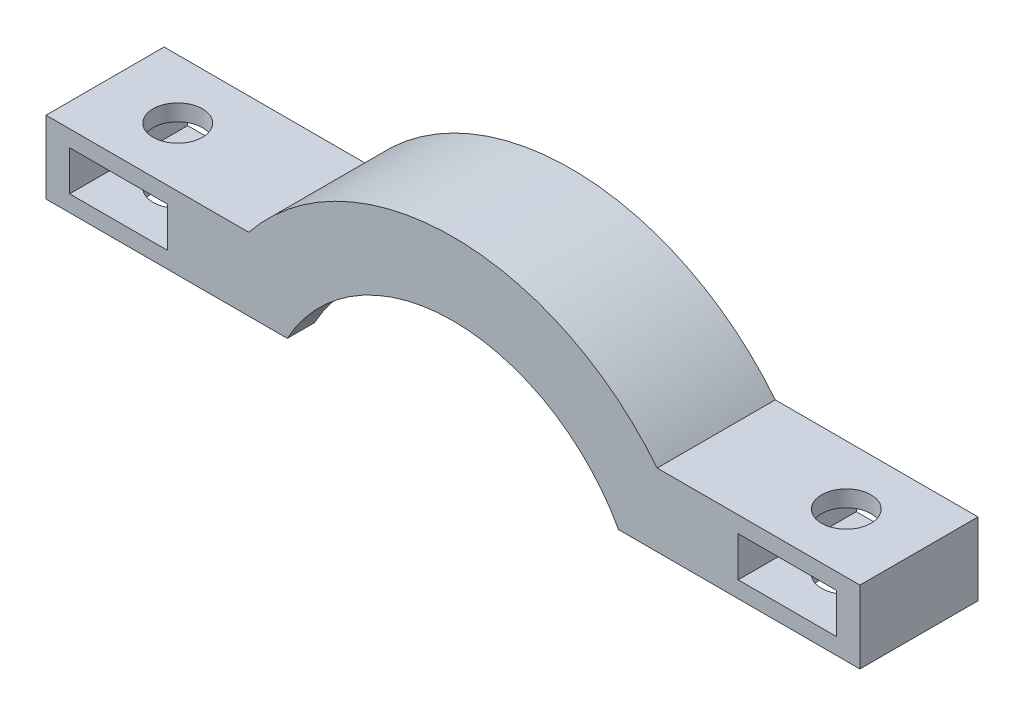
SolidWorks part; units mm, degrees
ref_plane "Front Plane" through (0, 0, 0) normal (0, 0, 1) x (1, 0, 0)
ref_plane "Top Plane" through (0, 0, 0) normal (0, 1, 0) x (1, 0, 0)
ref_plane "Right Plane" through (0, 0, 0) normal (1, 0, 0) x (0, 0, -1)
sketch "Sketch1" plane through (0, 0, 0) normal (0, 0, 1) x (1, 0, 0)
  circle A0 centre (0, 0) radius 18.288
  dimension "D1" = 36.576
extrude "Boss-Extrude1" add sketch "Sketch1" along normal blind 19.05
sketch "Sketch3" plane through (0, 0, 19.05) normal (0, 0, 1) x (1, 0, 0)
  circle A0 centre (0, 0) radius 13.208
  dimension "D2" = 26.416
extrude "Cut-Extrude1" cut sketch "Sketch3" against normal through all
ref_plane "Plane2" through (0, -13.716, 0) normal (0, 1, 0) x (1, 0, 0)
sketch "Sketch15" plane through (0, -13.716, 0) normal (0, 1, 0) x (1, 0, 0)
  line L0 (0, -19.05) -> (0, 0) construction
  line L1 (-9.525, -0.762) -> (9.525, -0.762)
  line L2 (-9.525, -0.762) -> (-9.525, -18.288)
  line L3 (-9.525, -18.288) -> (9.525, -18.288)
  line L4 (9.525, -0.762) -> (9.525, -18.288)
  line L5 (-9.525, -0.762) -> (9.525, -18.288) construction
  line L6 (-9.525, -18.288) -> (9.525, -0.762) construction
  line L7 (-13.208, -19.05) -> (13.208, -19.05) construction
  line L8 (18.288, 0) -> (-18.288, 0) construction
  point P0 (0, -9.525)
  dimension "D1" = 19.05
  dimension "D2" = 0.762
  dimension "D3" = 0.762
extrude "Boss-Extrude3" add sketch "Sketch15" against normal blind 15.24
sketch "Sketch16" plane through (0, 0, 18.288) normal (0, 0, 1) x (1, 0, 0)
  line L0 (-9.525, -28.956) -> (-9.525, -15.6117) construction
  line L1 (-5.715, -25.5076) -> (5.715, -25.5076)
  line L2 (-5.715, -25.5076) -> (-5.715, -19.6656)
  line L3 (-5.715, -19.6656) -> (5.715, -19.6656)
  line L4 (5.715, -25.5076) -> (5.715, -19.6656)
  line L5 (-5.715, -25.5076) -> (5.715, -19.6656) construction
  line L6 (-5.715, -19.6656) -> (5.715, -25.5076) construction
  point P0 (0, -22.5866)
  dimension "D1" = 5.842
  dimension "D2" = 11.43
  dimension "D3" = 3.81
extrude "Cut-Extrude4" cut sketch "Sketch16" against normal through all
chamfer "Chamfer1" distance 5.08 angle 58 1 edges at (0, -28.956, 0.762) first distance on face at (0, -28.956, 9.525)
hole_wizard "1/4 Clearance Hole1" positions "Sketch18" profile "Sketch17" hole size "1/4" standard "ANSI Inch" end condition up to next
sketch "Sketch18" plane through (0, -28.956, 0) normal (0, -1, 0) x (-1, 0, 0)
  line L0 (0, -18.288) -> (0, -0.762) construction
  point P0 (0, -12.0214)
sketch "Sketch17" plane through (0, -28.956, 12.0214) normal (1, 0, 0) x (0, 0, -1)
  line L0 (0, 0) -> (0, 3.4484)
  line L1 (0, 3.4484) -> (3.3782, 3.4484)
  line L2 (3.3782, 3.4484) -> (3.3782, 0)
  line L5 (3.3782, 0) -> (0, 0)
  line L11 (0, -6.35) -> (0, 107.95) construction
  dimension "Thru Hole Dia." = 6.7564
  dimension "Thru Hole Depth" = 3.4484
sketch "Sketch19" plane through (0, 0, 19.05) normal (0, 0, 1) x (1, 0, 0)
  circle A0 centre (0, 0) radius 18.288
  circle A1 centre (0, 0) radius 13.208
extrude "Cut-Extrude5" cut sketch "Sketch19" against normal up to surface (0.762 mm away) up to face at (0, -22.5866, 18.288)
sketch "Sketch20" plane through (0, 0, 18.288) normal (0, 0, 1) x (1, 0, 0)
  circle A0 centre (0, 0) radius 18.288
extrude "Cut-Extrude6" cut sketch "Sketch20" against normal blind 2.54
sketch "Sketch21" plane through (0, 0, 0) normal (0, 0, -1) x (-1, 0, 0)
  circle A0 centre (0, 0) radius 18.288
extrude "Cut-Extrude7" cut sketch "Sketch21" against normal offset from surface (7.493 mm away) 8.255 up to face at (0, 0, 15.748)
sketch "Sketch22" plane through (0, -13.716, 0) normal (0, 1, 0) x (1, 0, 0)
  line L0 (9.525, -7.493) -> (9.525, -0.762) construction
  line L1 (-9.525, -0.762) -> (9.525, -0.762)
  line L2 (-9.525, -0.762) -> (-9.525, -4.953)
  line L3 (-9.525, -4.953) -> (9.525, -4.953)
  line L4 (9.525, -0.762) -> (9.525, -4.953)
  line L5 (18.288, -7.493) -> (-18.288, -7.493) construction
  dimension "D1" = 2.54
extrude "Cut-Extrude8" cut sketch "Sketch22" against normal through all
ref_plane "Plane3" through (0, 0, 13.843) normal (0, 0, 1) x (1, 0, 0)
sketch "Sketch24" plane through (0, 0, 13.843) normal (0, 0, 1) x (1, 0, 0)
  circle A0 centre (0, 0) radius 14.478
  circle A1 centre (0, 0) radius 13.208 construction
  dimension "D1" = 1.27
extrude "Cut-Extrude10" cut sketch "Sketch24" against normal blind 5.334
ref_plane "Plane4" through (0, -6.35, 0) normal (0, 1, 0) x (1, 0, 0)
ref_plane "Plane5" through (0, 6.35, 0) normal (0, 1, 0) x (1, 0, 0)
ref_plane "Plane6" through (13.208, 0, 0) normal (1, 0, 0) x (0, 0, -1)
sketch "Sketch25" plane through (13.208, 0, 0) normal (1, 0, 0) x (0, 0, -1)
  line L0 (-15.748, 18.288) -> (-15.748, -15.6117) construction
  line L1 (-15.748, 11.43) -> (-7.493, 11.43)
  line L2 (-15.748, 11.43) -> (-15.748, 6.35)
  line L3 (-15.748, 6.35) -> (-7.493, 6.35)
  line L4 (-7.493, 11.43) -> (-7.493, 6.35)
  line L5 (7.3343, 6.35) -> (-7.3343, 6.35) construction
  line L6 (-7.493, -15.6117) -> (-7.493, 18.288) construction
  line L7 (7.3343, -6.35) -> (-7.3343, -6.35) construction
  line L8 (-15.748, -11.43) -> (-7.493, -11.43)
  line L9 (-15.748, -11.43) -> (-15.748, -6.35)
  line L10 (-15.748, -6.35) -> (-7.493, -6.35)
  line L11 (-7.493, -11.43) -> (-7.493, -6.35)
  dimension "D1" = 5.08
  dimension "D2" = 5.08
extrude "Boss-Extrude4" add sketch "Sketch25" along normal blind 15.24
hole_wizard "#4 Clearance Hole1" positions "Sketch27" profile "Sketch26" hole size "#4" standard "ANSI Inch" end condition through all
sketch "Sketch27" plane through (0, -11.43, 0) normal (0, -1, 0) x (-1, 0, 0)
  line L0 (-28.448, -15.748) -> (-14.2761, -15.748) construction
  line L1 (-28.448, -15.748) -> (-28.448, -7.493) construction
  line L2 (-14.2761, -15.748) -> (-14.2761, -7.493) construction
  point P0 (-23.368, -11.6205)
  dimension "D1" = 4.1275
  dimension "D2" = 5.08
  dimension "D3" = 9.0919
sketch "Sketch26" plane through (23.368, -11.43, 11.6205) normal (1, 0, 0) x (0, 0, -1)
  line L0 (0, 0) -> (0, 29.718)
  line L1 (0, 29.718) -> (1.7272, 29.718)
  line L2 (1.7272, 29.718) -> (1.7272, 0)
  line L5 (1.7272, 0) -> (0, 0)
  line L11 (0, -6.35) -> (0, 107.95) construction
  dimension "Thru Hole Dia." = 3.4544
  dimension "Thru Hole Depth" = 29.718
sketch "Sketch28" plane through (0, 0, 15.748) normal (0, 0, 1) x (1, 0, 0)
  line L0 (23.368, -6.35) -> (23.368, -11.43) construction
  line L1 (19.939, -10.287) -> (26.797, -10.287)
  line L2 (19.939, -10.287) -> (19.939, -7.493)
  line L3 (19.939, -7.493) -> (26.797, -7.493)
  line L4 (26.797, -10.287) -> (26.797, -7.493)
  line L5 (19.939, -10.287) -> (26.797, -7.493) construction
  line L6 (19.939, -7.493) -> (26.797, -10.287) construction
  line L7 (7.3343, -6.35) -> (-7.3343, -6.35) construction
  point P0 (23.368, -8.89)
  dimension "D1" = 2.794
  dimension "D2" = 6.858
  dimension "D3" = 1.143
extrude "Cut-Extrude11" cut sketch "Sketch28" against normal through all
mirror "Mirror2" about plane through (0, 0, 0) normal (0, 1, 0) of "Cut-Extrude11"
mirror "Mirror3" about plane through (0, 0, 0) normal (1, 0, 0) of "Mirror2", "Cut-Extrude11", "#4 Clearance Hole1", "Boss-Extrude4"
sketch "Sketch29" plane through (0, -28.956, 0) normal (0, -1, 0) x (1, 0, 0)
  line L1 (-39.8759, 23.7895) -> (38.2946, 23.7895)
  line L2 (-39.8759, 23.7895) -> (-39.8759, -5.6362)
  line L3 (-39.8759, -5.6362) -> (38.2946, -5.6362)
  line L4 (38.2946, 23.7895) -> (38.2946, -5.6362)
extrude "Cut-Extrude12" cut sketch "Sketch29" against normal up to surface (35.306 mm away) up to face at (-23.368, 6.35, 9.8933)
chamfer "Chamfer2" distance 1.27 angle 45 2 edges at (0, 14.478, 8.509) (0, 14.478, 13.843)
